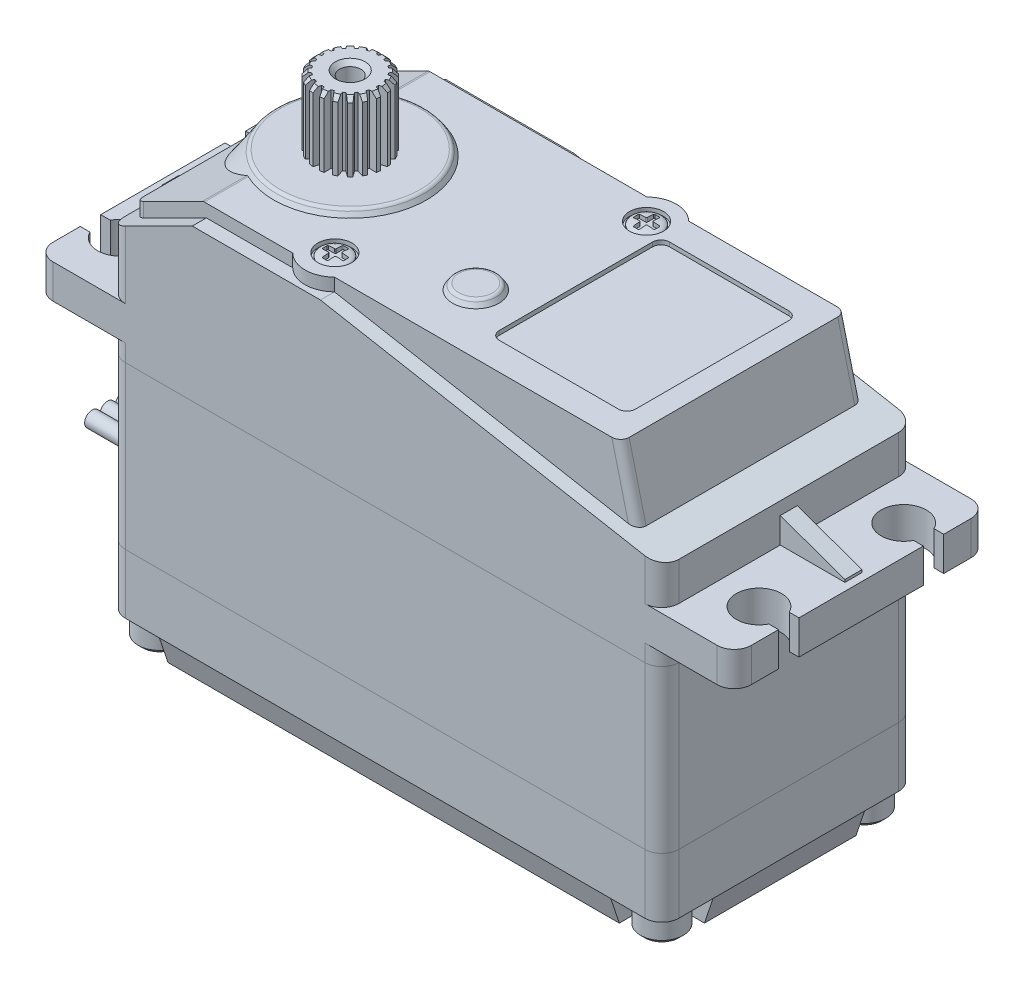
SolidWorks part; units mm, degrees
other "Markup1"
sketch "Sketch20" plane through (60, 8.7, -14.9) normal (0.2547, 0.9537, -0.1598) x (-0.9305, 0.2867, 0.228)
ref_plane "Front Plane" through (0, 0, 0) normal (0, 0, 1) x (1, 0, 0)
ref_plane "Top Plane" through (0, 0, 0) normal (0, 1, 0) x (1, 0, 0)
ref_plane "Right Plane" through (0, 0, 0) normal (1, 0, 0) x (0, 0, -1)
sketch "Sketch1" plane through (0, 0, 0) normal (0, 1, 0) x (1, 0, 0)
  line L0 (11.399, -13.25) -> (47, -13.25)
  line L1 (-12, 13.25) -> (21.601, 13.25)
  line L2 (-12, 13.25) -> (-12, -13.25)
  line L3 (-12, -13.25) -> (6.5, -13.25)
  line L4 (47, 13.25) -> (47, -13.25)
  line L5 (-12, 13.25) -> (47, -13.25) construction
  line L6 (-12, -13.25) -> (47, 13.25) construction
  line L7 (26.5, 13.25) -> (47, 13.25)
  arc A0 (6.5, -13.25) -> (11.399, -13.25) centre (8.9495, -10.75) ccw
  arc A1 (26.5, 13.25) -> (21.601, 13.25) centre (24.0505, 10.75) ccw
  point P0 (17.5, 0)
  dimension "D4" = 7
  dimension "D1" = 59
  dimension "D2" = 26.5
  dimension "D3" = 47
  dimension "D5" = 2.5
  dimension "D6" = 2.5
  dimension "D7" = 18.5
  dimension "D8" = 20.5
extrude "Boss-Extrude1" add sketch "Sketch1" against normal blind 8
chamfer "Chamfer1" distance 4 distance2 8 1 edges at (-12, 0, 0) first distance on face at (-12, -4, 0)
chamfer "Chamfer2" distance 8 distance2 2 1 edges at (47, 0, 0) first distance on face at (47, -4, 0)
fillet "Fillet1" radius 1 4 edges at (46, -4, -13.25) (46, -4, 13.25) (-12, -6, -13.25) (-12, -6, 13.25)
sketch "Sketch2" plane through (0, 0, 0) normal (0, 1, 0) x (1, 0, 0)
  line L0 (21, -8.5) -> (0, -8.5) construction
  circle A0 centre (0, 0) radius 8.5
  circle A1 centre (21, -6.25) radius 2.25
  dimension "D1" = 17
  dimension "D2" = 4.5
  dimension "D3" = 21
extrude "Boss-Extrude2" add sketch "Sketch2" against normal blind 5 draft 34 from offset 0.7 draft outward yes
fillet "Fillet2" radius 0.5 1 edges at (21, 0.7, 8.5)
sketch "Sketch3" plane through (0, 0, 0) normal (0, 0, 1) x (1, 0, 0)
  line L0 (-3.6459, -1.5) -> (-13.5, -6.4271)
  line L1 (-13.5, -6.4271) -> (-13.5, -13.3216)
  line L2 (-13.5, -13.3216) -> (-22, -13.3216)
  line L3 (-22, -13.3216) -> (-22, -17.3216)
  line L4 (-22, -17.3216) -> (-13.5, -17.3216)
  line L5 (-13.5, -17.3216) -> (-13.5, -19.3216)
  line L6 (-13.5, -19.3216) -> (51.5, -19.3216)
  line L7 (51.5, -19.3216) -> (51.5, -17.3216)
  line L8 (51.5, -17.3216) -> (60, -17.3216)
  line L9 (60, -17.3216) -> (60, -13.3216)
  line L10 (60, -13.3216) -> (51.5, -13.3216)
  line L11 (51.5, -13.3216) -> (51.5, -8.8216)
  line L12 (51.5, -8.8216) -> (11.399, -1.5)
  line L13 (11.399, -8) -> (11.399, 0) construction
  line L14 (11.399, -1.5) -> (-3.6459, -1.5)
  line L15 (-4, 0) -> (-11, -3.5) construction
  line L16 (-4, 0) -> (6.5, 0) construction
  line L17 (-12, -8) -> (-12, -4) construction
  dimension "D1" = 2
  dimension "D2" = 4
  dimension "D3" = 4.5
  dimension "D4" = 1.5
  dimension "D5" = 1.5
  dimension "D6" = 1.5
  dimension "D7" = 65
  dimension "D8" = 8.5
extrude "Boss-Extrude3" add sketch "Sketch3" along normal mid plane 29.8
fillet "Fillet3" radius 2 12 edges at (60, -15.3216, -14.9) (60, -15.3216, 14.9) (-22, -15.3216, 14.9) (-22, -15.3216, -14.9) (51.5, -18.3216, 14.9) (51.5, -18.3216, -14.9) (-13.5, -18.3216, 14.9) (-13.5, -18.3216, -14.9) (-13.5, -9.8743, -14.9) (-13.5, -9.8743, 14.9) (51.5, -11.0716, -14.9) (51.5, -11.0716, 14.9)
sketch "Sketch4" plane through (0, 0, 0) normal (0, 1, 0) x (1, 0, 0)
  line L0 (45, -12.25) -> (45, 12.25) construction
  line L1 (27.5, 10) -> (41.5, 10)
  line L2 (26.5, 9) -> (26.5, -9)
  line L3 (27.5, -10) -> (41.5, -10)
  line L4 (42.5, 9) -> (42.5, -9)
  line L5 (26.5, 10) -> (42.5, -10) construction
  line L6 (26.5, -10) -> (42.5, 10) construction
  circle A0 centre (24.0505, 10.75) radius 2
  circle A1 centre (8.9495, -10.75) radius 2
  arc A2 (41.5, 10) -> (42.5, 9) centre (41.5, 9) cw
  arc A3 (27.5, 10) -> (26.5, 9) centre (27.5, 9) ccw
  arc A4 (26.5, -9) -> (27.5, -10) centre (27.5, -9) ccw
  arc A5 (41.5, -10) -> (42.5, -9) centre (41.5, -9) ccw
  point P0 (34.5, 0)
  dimension "D1" = 4
  dimension "D5" = 1
  dimension "D2" = 20
  dimension "D3" = 16
  dimension "D4" = 2.5
extrude "Cut-Extrude1" cut sketch "Sketch4" against normal blind 0.5
sketch "Sketch5" plane through (0, -13.3216, 0) normal (0, 1, 0) x (1, 0, 0)
  line L0 (-22, 0) -> (60, 0) construction
  line L1 (-22, -12.9) -> (-22, 12.9) construction
  line L2 (60, -12.9) -> (60, 12.9) construction
  line L3 (19, 0) -> (19, 21.0756) construction
  line L4 (58.8627, -7.3) -> (60, -7.3)
  line L5 (58.8627, -9.7) -> (60, -9.7)
  line L6 (60, -9.7) -> (60, -7.3)
  line L7 (60, 9.7) -> (60, 7.3)
  line L8 (58.8627, 9.7) -> (60, 9.7)
  line L9 (58.8627, 7.3) -> (60, 7.3)
  line L10 (-20.8627, 7.3) -> (-22, 7.3)
  line L11 (-20.8627, 9.7) -> (-22, 9.7)
  line L12 (-22, 9.7) -> (-22, 7.3)
  line L13 (-22, -9.7) -> (-22, -7.3)
  line L14 (-20.8627, -9.7) -> (-22, -9.7)
  line L15 (-20.8627, -7.3) -> (-22, -7.3)
  arc A0 (58.8627, -7.3) -> (58.8627, -9.7) centre (56.5, -8.5) ccw
  arc A1 (58.8627, 7.3) -> (58.8627, 9.7) centre (56.5, 8.5) cw
  arc A2 (-20.8627, 7.3) -> (-20.8627, 9.7) centre (-18.5, 8.5) ccw
  arc A3 (-20.8627, -7.3) -> (-20.8627, -9.7) centre (-18.5, -8.5) cw
  dimension "D1" = 17
  dimension "D3" = 5.3
  dimension "D2" = 75
  dimension "D4" = 2.4
extrude "Cut-Extrude2" cut sketch "Sketch5" against normal through all
sketch "Sketch6" plane through (0, -19.3216, 0) normal (0, -1, 0) x (1, 0, 0)
  line L4 (51.5, -12.9) -> (51.5, 12.9)
  line L5 (49.5, 14.9) -> (-11.5, 14.9)
  line L6 (-13.5, 12.9) -> (-13.5, -12.9)
  line L7 (-11.5, -14.9) -> (49.5, -14.9)
  line L8 (51.5, -12.9) -> (51.5, 12.9)
  line L9 (49.5, 14.9) -> (-11.5, 14.9)
  line L10 (-13.5, 12.9) -> (-13.5, -12.9)
  line L11 (-11.5, -14.9) -> (49.5, -14.9)
  arc A4 (51.5, 12.9) -> (49.5, 14.9) centre (49.5, 12.9) ccw
  arc A5 (-11.5, 14.9) -> (-13.5, 12.9) centre (-11.5, 12.9) ccw
  arc A6 (-13.5, -12.9) -> (-11.5, -14.9) centre (-11.5, -12.9) ccw
  arc A7 (49.5, -14.9) -> (51.5, -12.9) centre (49.5, -12.9) ccw
  arc A8 (51.5, 12.9) -> (49.5, 14.9) centre (49.5, 12.9) ccw
  arc A9 (-11.5, 14.9) -> (-13.5, 12.9) centre (-11.5, 12.9) ccw
  arc A10 (-13.5, -12.9) -> (-11.5, -14.9) centre (-11.5, -12.9) ccw
  arc A11 (49.5, -14.9) -> (51.5, -12.9) centre (49.5, -12.9) ccw
  dimension "D1" = 0
extrude "Boss-Extrude4" add sketch "Sketch6" along normal blind 19 separate body
sketch "Sketch7" plane through (0, -38.3216, 0) normal (0, -1, 0) x (1, 0, 0)
  line L4 (51.5, -12.9) -> (51.5, 12.9)
  line L5 (49.5, 14.9) -> (-11.5, 14.9)
  line L6 (-13.5, 12.9) -> (-13.5, -12.9)
  line L7 (-11.5, -14.9) -> (49.5, -14.9)
  line L8 (51.5, -12.9) -> (51.5, 12.9)
  line L9 (49.5, 14.9) -> (-11.5, 14.9)
  line L10 (-13.5, 12.9) -> (-13.5, -12.9)
  line L11 (-11.5, -14.9) -> (49.5, -14.9)
  arc A4 (49.5, -14.9) -> (51.5, -12.9) centre (49.5, -12.9) ccw
  arc A5 (51.5, 12.9) -> (49.5, 14.9) centre (49.5, 12.9) ccw
  arc A6 (-11.5, 14.9) -> (-13.5, 12.9) centre (-11.5, 12.9) ccw
  arc A7 (-13.5, -12.9) -> (-11.5, -14.9) centre (-11.5, -12.9) ccw
  arc A8 (49.5, -14.9) -> (51.5, -12.9) centre (49.5, -12.9) ccw
  arc A9 (51.5, 12.9) -> (49.5, 14.9) centre (49.5, 12.9) ccw
  arc A10 (-11.5, 14.9) -> (-13.5, 12.9) centre (-11.5, 12.9) ccw
  arc A11 (-13.5, -12.9) -> (-11.5, -14.9) centre (-11.5, -12.9) ccw
  dimension "D1" = 0
extrude "Boss-Extrude5" add sketch "Sketch7" along normal blind 10 separate body
sketch "Sketch11" plane through (0, 0, 0) normal (0, 0, 1) x (1, 0, 0)
  line L0 (51.5, -10.3216) -> (59.1, -13.0216)
  line L2 (51.5, -13.3216) -> (51.5, -8.8216) construction
  line L3 (58, -13.3216) -> (49.5, -13.3216) construction
  line L5 (19, -19.3216) -> (19, 14.0066) construction
  line L6 (-11.5, -19.3216) -> (49.5, -19.3216) construction
  line L7 (-21.1, -13.0216) -> (-21.1, -13.3216)
  line L8 (59.1, -13.3216) -> (51.5, -13.3216)
  line L9 (51.5, -13.3216) -> (51.5, -10.3216)
  line L10 (51.5, -10.3216) -> (51.5171, -10.3436)
  line L11 (-13.5, -10.3216) -> (-13.5171, -10.3436)
  line L12 (-13.5, -13.3216) -> (-13.5, -10.3216)
  line L13 (-21.1, -13.3216) -> (-13.5, -13.3216)
  line L14 (59.1, -13.0216) -> (59.1, -13.3216)
  line L15 (-13.5, -10.3216) -> (-21.1, -13.0216)
  dimension "D1" = 7.6
  dimension "D2" = 3
  dimension "D3" = 0.3
extrude "Boss-Extrude6" add sketch "Sketch11" along normal mid plane 2 contours L9 L8 L0 | L15 L7 L13 L12 region at (54.2636, -12.3125, 0) region at (-16.2636, -12.3125, 0)
sketch "Sketch12" plane through (0, -48.3216, 0) normal (0, -1, 0) x (1, 0, 0)
  line L0 (65.179, 0) -> (19, 0) construction
  line L1 (49.5, 14.9) -> (-11.5, 14.9) construction
  line L2 (19, 0) -> (19, 14.9) construction
  line L4 (45.5, 14.9) -> (45.5, 8.9)
  line L6 (45.5, 8.9) -> (51.5, 8.9)
  line L9 (45.5, 14.9) -> (49.5, 14.9)
  line L10 (51.5, 12.9) -> (51.5, 8.9)
  line L11 (47.25, -11.1783) -> (48.5, -10.4566)
  line L12 (48.5, 10.4566) -> (49.75, 11.1783)
  line L13 (49.75, 11.1783) -> (49.75, 12.6217)
  line L14 (49.75, 12.6217) -> (48.5, 13.3434)
  line L15 (48.5, 13.3434) -> (47.25, 12.6217)
  line L16 (47.25, 12.6217) -> (47.25, 11.1783)
  line L17 (47.25, 11.1783) -> (48.5, 10.4566)
  line L18 (47.25, -12.6217) -> (47.25, -11.1783)
  line L19 (48.5, -13.3434) -> (47.25, -12.6217)
  line L20 (49.75, -12.6217) -> (48.5, -13.3434)
  line L21 (49.75, -11.1783) -> (49.75, -12.6217)
  line L22 (48.5, -10.4566) -> (49.75, -11.1783)
  line L23 (51.5, -12.9) -> (51.5, -8.9)
  line L24 (45.5, -14.9) -> (49.5, -14.9)
  line L25 (45.5, -8.9) -> (51.5, -8.9)
  line L26 (45.5, -14.9) -> (45.5, -8.9)
  line L27 (-7.5, -14.9) -> (-7.5, -8.9)
  line L28 (-7.5, -8.9) -> (-13.5, -8.9)
  line L29 (-7.5, -14.9) -> (-11.5, -14.9)
  line L30 (-13.5, -12.9) -> (-13.5, -8.9)
  line L31 (-10.5, -10.4566) -> (-11.75, -11.1783)
  line L32 (-11.75, -11.1783) -> (-11.75, -12.6217)
  line L33 (-11.75, -12.6217) -> (-10.5, -13.3434)
  line L34 (-10.5, -13.3434) -> (-9.25, -12.6217)
  line L35 (-9.25, -12.6217) -> (-9.25, -11.1783)
  line L36 (-9.25, 11.1783) -> (-10.5, 10.4566)
  line L37 (-9.25, 12.6217) -> (-9.25, 11.1783)
  line L38 (-10.5, 13.3434) -> (-9.25, 12.6217)
  line L39 (-11.75, 12.6217) -> (-10.5, 13.3434)
  line L40 (-11.75, 11.1783) -> (-11.75, 12.6217)
  line L41 (-10.5, 10.4566) -> (-11.75, 11.1783)
  line L42 (-9.25, -11.1783) -> (-10.5, -10.4566)
  line L43 (-13.5, 12.9) -> (-13.5, 8.9)
  line L44 (-7.5, 14.9) -> (-11.5, 14.9)
  line L45 (-7.5, 8.9) -> (-13.5, 8.9)
  line L46 (-7.5, 14.9) -> (-7.5, 8.9)
  line L47 (49.5, 14.9) -> (-11.5, 14.9) construction
  line L48 (51.5, -12.9) -> (51.5, 12.9) construction
  arc A0 (51.5, 12.9) -> (49.5, 14.9) centre (49.5, 12.9) ccw construction
  arc A1 (51.5, 12.9) -> (49.5, 14.9) centre (49.5, 12.9) ccw
  circle A2 centre (48.5, 11.9) radius 2.5
  circle A3 centre (48.5, 11.9) radius 1.25 construction
  circle A4 centre (48.5, -11.9) radius 1.25 construction
  circle A5 centre (48.5, -11.9) radius 2.5
  arc A6 (51.5, -12.9) -> (49.5, -14.9) centre (49.5, -12.9) cw
  circle A7 centre (-10.5, -11.9) radius 1.25 construction
  circle A8 centre (-10.5, 11.9) radius 1.25 construction
  arc A9 (-13.5, -12.9) -> (-11.5, -14.9) centre (-11.5, -12.9) ccw
  circle A10 centre (-10.5, -11.9) radius 2.5
  circle A11 centre (-10.5, 11.9) radius 2.5
  arc A12 (-13.5, 12.9) -> (-11.5, 14.9) centre (-11.5, 12.9) cw
  point P21 (48.5, 8.9)
  point P23 (45.5, 11.9)
  dimension "D2" = 5
  dimension "D3" = 2.5
  dimension "D1" = 6
extrude "Cut-Extrude3" cut sketch "Sketch12" against normal blind 3 contours A11 L45 L46 | A12 L43 L45 A11 L46 L44 | L41 L36 L37 L38 L39 L40 | A10 L28 L30 A9 L29 L27 | A10 L27 L28 | L35 L42 L31 L32 L33 L34 | A6 L23 L25 A5 L26 L24 | A5 L25 L26 | L22 L11 L18 L19 L20 L21 | L16 L17 L12 L13 L14 L15 | A2 L4 L6 | A2 L6 L10 A1 L9 L4 region at (47.5, -48.3216, 14.8151) region at (48.5, -48.3216, -11.9) region at (48.5, -48.3216, 11.9) region at (50.8542, -48.3216, -14.2542) region at (-9.5, -48.3216, -14.8151) region at (-10.5, -48.3216, -11.9) region at (-10.5, -48.3216, 11.9) region at (-12.8542, -48.3216, 14.2542)
chamfer "Chamfer4" distance 3 distance2 1 4 edges at (51.5, -48.3216, 0) (19, -48.3216, -14.9) (-13.5, -48.3216, 0) (19, -48.3216, 14.9) first distance on face at (51.5, -44.3216, 0) first distance on face at (19, -44.3216, -14.9) first distance on face at (-13.5, -44.3216, 0) first distance on face at (19, -44.3216, 14.9)
chamfer "Chamfer5" distance 0.5 angle 45 4 edges at (-10.5, -48.3216, -14.4) (-10.5, -48.3216, 9.4) (48.5, -48.3216, 9.4) (48.5, -48.3216, -14.4)
sketch "Sketch13" plane through (0, 0.7, 0) normal (0, 1, 0) x (1, 0, 0)
  circle A0 centre (0, 0) radius 4
  circle A1 centre (0, 0) radius 1.25
  dimension "D1" = 8
  dimension "D2" = 2.5
extrude "Boss-Extrude7" add sketch "Sketch13" along normal blind 8 separate body
chamfer "Chamfer6" distance 0.5 angle 45 2 edges at (0, 8.7, 4) (0, 8.7, 1.25)
sketch "Sketch14" plane through (0, 8.7, 0) normal (0, 1, 0) x (1, 0, 0)
  line L0 (3.9799, 0.4) -> (3.2, 0.15)
  line L1 (3.2, 0.15) -> (3.2, -0.15)
  line L2 (3.2, -0.15) -> (3.9799, -0.4)
  line L3 (3.2, 0) -> (0, 0) construction
  line L4 (3.9088, -0.8494) -> (3.0897, -0.8462)
  line L5 (3.0897, -0.8462) -> (2.997, -1.1315)
  line L6 (2.997, -1.1315) -> (3.6616, -1.6103)
  line L7 (3.455, -2.0157) -> (2.677, -1.7596)
  line L8 (2.677, -1.7596) -> (2.5007, -2.0023)
  line L9 (2.5007, -2.0023) -> (2.9847, -2.663)
  line L10 (2.663, -2.9847) -> (2.0023, -2.5007)
  line L11 (2.0023, -2.5007) -> (1.7596, -2.677)
  line L12 (1.7596, -2.677) -> (2.0157, -3.455)
  line L13 (1.6103, -3.6616) -> (1.1315, -2.997)
  line L14 (1.1315, -2.997) -> (0.8462, -3.0897)
  line L15 (0.8462, -3.0897) -> (0.8494, -3.9088)
  line L16 (0.4, -3.9799) -> (0.15, -3.2)
  line L17 (0.15, -3.2) -> (-0.15, -3.2)
  line L18 (-0.15, -3.2) -> (-0.4, -3.9799)
  line L19 (-0.8494, -3.9088) -> (-0.8462, -3.0897)
  line L20 (-0.8462, -3.0897) -> (-1.1315, -2.997)
  line L21 (-1.1315, -2.997) -> (-1.6103, -3.6616)
  line L22 (-2.0157, -3.455) -> (-1.7596, -2.677)
  line L23 (-1.7596, -2.677) -> (-2.0023, -2.5007)
  line L24 (-2.0023, -2.5007) -> (-2.663, -2.9847)
  line L25 (-2.9847, -2.663) -> (-2.5007, -2.0023)
  line L26 (-2.5007, -2.0023) -> (-2.677, -1.7596)
  line L27 (-2.677, -1.7596) -> (-3.455, -2.0157)
  line L28 (-3.6616, -1.6103) -> (-2.997, -1.1315)
  line L29 (-2.997, -1.1315) -> (-3.0897, -0.8462)
  line L30 (-3.0897, -0.8462) -> (-3.9088, -0.8494)
  line L31 (-3.9799, -0.4) -> (-3.2, -0.15)
  line L32 (-3.2, -0.15) -> (-3.2, 0.15)
  line L33 (-3.2, 0.15) -> (-3.9799, 0.4)
  line L34 (-3.9088, 0.8494) -> (-3.0897, 0.8462)
  line L35 (-3.0897, 0.8462) -> (-2.997, 1.1315)
  line L36 (-2.997, 1.1315) -> (-3.6616, 1.6103)
  line L37 (-3.455, 2.0157) -> (-2.677, 1.7596)
  line L38 (-2.677, 1.7596) -> (-2.5007, 2.0023)
  line L39 (-2.5007, 2.0023) -> (-2.9847, 2.663)
  line L40 (-2.663, 2.9847) -> (-2.0023, 2.5007)
  line L41 (-2.0023, 2.5007) -> (-1.7596, 2.677)
  line L42 (-1.7596, 2.677) -> (-2.0157, 3.455)
  line L43 (-1.6103, 3.6616) -> (-1.1315, 2.997)
  line L44 (-1.1315, 2.997) -> (-0.8462, 3.0897)
  line L45 (-0.8462, 3.0897) -> (-0.8494, 3.9088)
  line L46 (-0.4, 3.9799) -> (-0.15, 3.2)
  line L47 (-0.15, 3.2) -> (0.15, 3.2)
  line L48 (0.15, 3.2) -> (0.4, 3.9799)
  line L49 (0.8494, 3.9088) -> (0.8462, 3.0897)
  line L50 (0.8462, 3.0897) -> (1.1315, 2.997)
  line L51 (1.1315, 2.997) -> (1.6103, 3.6616)
  line L52 (2.0157, 3.455) -> (1.7596, 2.677)
  line L53 (1.7596, 2.677) -> (2.0023, 2.5007)
  line L54 (2.0023, 2.5007) -> (2.663, 2.9847)
  line L55 (2.9847, 2.663) -> (2.5007, 2.0023)
  line L56 (2.5007, 2.0023) -> (2.677, 1.7596)
  line L57 (2.677, 1.7596) -> (3.455, 2.0157)
  line L58 (3.6616, 1.6103) -> (2.997, 1.1315)
  line L59 (2.997, 1.1315) -> (3.0897, 0.8462)
  line L60 (3.0897, 0.8462) -> (3.9088, 0.8494)
  circle A0 centre (0, 0) radius 4 construction
  arc A1 (3.9799, -0.4) -> (3.9799, 0.4) centre (0, 0) ccw
  arc A2 (3.6616, -1.6103) -> (3.9088, -0.8494) centre (0, 0) ccw
  arc A3 (2.9847, -2.663) -> (3.455, -2.0157) centre (0, 0) ccw
  arc A4 (2.0157, -3.455) -> (2.663, -2.9847) centre (0, 0) ccw
  arc A5 (0.8494, -3.9088) -> (1.6103, -3.6616) centre (0, 0) ccw
  arc A6 (-0.4, -3.9799) -> (0.4, -3.9799) centre (0, 0) ccw
  arc A7 (-1.6103, -3.6616) -> (-0.8494, -3.9088) centre (0, 0) ccw
  arc A8 (-2.663, -2.9847) -> (-2.0157, -3.455) centre (0, 0) ccw
  arc A9 (-3.455, -2.0157) -> (-2.9847, -2.663) centre (0, 0) ccw
  arc A10 (-3.9088, -0.8494) -> (-3.6616, -1.6103) centre (0, 0) ccw
  arc A11 (-3.9799, 0.4) -> (-3.9799, -0.4) centre (0, 0) ccw
  arc A12 (-3.6616, 1.6103) -> (-3.9088, 0.8494) centre (0, 0) ccw
  arc A13 (-2.9847, 2.663) -> (-3.455, 2.0157) centre (0, 0) ccw
  arc A14 (-2.0157, 3.455) -> (-2.663, 2.9847) centre (0, 0) ccw
  arc A15 (-0.8494, 3.9088) -> (-1.6103, 3.6616) centre (0, 0) ccw
  arc A16 (0.4, 3.9799) -> (-0.4, 3.9799) centre (0, 0) ccw
  arc A17 (1.6103, 3.6616) -> (0.8494, 3.9088) centre (0, 0) ccw
  arc A18 (2.663, 2.9847) -> (2.0157, 3.455) centre (0, 0) ccw
  arc A19 (3.455, 2.0157) -> (2.9847, 2.663) centre (0, 0) ccw
  arc A20 (3.9088, 0.8494) -> (3.6616, 1.6103) centre (0, 0) ccw
  point P85 (0, 0)
  dimension "D1" = 0.3
  dimension "D2" = 0.8
  dimension "D3" = 3.2
  dimension "D4" = 20
extrude "Cut-Extrude4" cut sketch "Sketch14" against normal through all
sketch "Sketch15" plane through (0, -0.5, 0) normal (0, 1, 0) x (1, 0, 0)
  circle A0 centre (8.9495, -10.75) radius 1.75
  circle A1 centre (8.9495, -10.75) radius 2 construction
  circle A2 centre (24.0505, 10.75) radius 2 construction
  circle A5 centre (24.0505, 10.75) radius 1.75
  dimension "D1" = 3.5
extrude "Boss-Extrude8" add sketch "Sketch15" along normal blind 0.5 separate body
fillet "Fillet4" radius 0.32 1 edges at (8.9495, 0, 12.5) second distance 1.2 first distance on face at (8.9495, 0, 12.5)
fillet "Fillet5" radius 0.32 1 edges at (24.0505, 0, -9) second distance 1.2 first distance on face at (24.0505, 0, -9)
sketch "Sketch16" plane through (0, 0, 0) normal (0, 1, 0) x (1, 0, 0)
  line L0 (8.607, -9.4483) -> (9.307, -9.4483)
  line L1 (23.7005, 12) -> (24.4005, 12)
  line L2 (23.7005, 12) -> (23.7005, 9.5)
  line L3 (23.7005, 9.5) -> (24.4005, 9.5)
  line L4 (24.4005, 12) -> (24.4005, 9.5)
  line L5 (23.7005, 12) -> (24.4005, 9.5) construction
  line L6 (23.7005, 9.5) -> (24.4005, 12) construction
  line L7 (22.8005, 11.1) -> (25.3005, 11.1)
  line L8 (22.8005, 11.1) -> (22.8005, 10.4)
  line L9 (22.8005, 10.4) -> (25.3005, 10.4)
  line L10 (25.3005, 11.1) -> (25.3005, 10.4)
  line L11 (22.8005, 11.1) -> (25.3005, 10.4) construction
  line L12 (22.8005, 10.4) -> (25.3005, 11.1) construction
  line L13 (8.607, -9.4483) -> (8.607, -11.9483)
  line L14 (8.607, -11.9483) -> (9.307, -11.9483)
  line L15 (9.307, -9.4483) -> (9.307, -11.9483)
  line L16 (8.607, -9.4483) -> (9.307, -11.9483) construction
  line L17 (8.607, -11.9483) -> (9.307, -9.4483) construction
  line L18 (7.707, -10.3483) -> (10.207, -10.3483)
  line L19 (7.707, -10.3483) -> (7.707, -11.0483)
  line L20 (7.707, -11.0483) -> (10.207, -11.0483)
  line L21 (10.207, -10.3483) -> (10.207, -11.0483)
  line L22 (7.707, -10.3483) -> (10.207, -11.0483) construction
  line L23 (7.707, -11.0483) -> (10.207, -10.3483) construction
  point P0 (24.0505, 10.75)
  point P5 (24.0505, 10.75)
  point P11 (8.957, -10.6983)
  point P16 (8.957, -10.6983)
  dimension "D1" = 2.5
  dimension "D2" = 0.7
  dimension "D3" = 2.5
  dimension "D4" = 0.7
extrude "Cut-Extrude5" cut sketch "Sketch16" against normal blind 0.48 contours L15 L14 L13 L0 | L20 L21 L18 L19 | L9 L10 L7 L8 | L4 L3 L2 L1
fillet "Fillet6" radius 0.1 12 edges at (24.4005, -0.24, -10.4) (24.4005, -0.24, -11.1) (23.7005, -0.24, -10.4) (23.7005, -0.24, -11.1) (23.7005, -0.2749, -12) (24.4005, -0.2749, -12) (25.3005, -0.2749, -11.1) (25.3005, -0.2749, -10.4) (24.4005, -0.2749, -9.5) (23.7005, -0.2749, -9.5) (22.8005, -0.2749, -10.4) (22.8005, -0.2749, -11.1)
fillet "Fillet7" radius 0.1 12 edges at (10.207, -0.2773, 10.3483) (9.307, -0.2701, 11.9483) (10.207, -0.2743, 11.0483) (7.707, -0.2728, 11.0483) (8.607, -0.2697, 11.9483) (9.307, -0.24, 11.0483) (8.607, -0.24, 11.0483) (7.707, -0.2757, 10.3483) (8.607, -0.2803, 9.4483) (8.607, -0.24, 10.3483) (9.307, -0.24, 10.3483) (9.307, -0.2807, 9.4483)
fillet "Fillet8" radius 0.5 3 edges at (0, 0.7, 8.5) (-4, 0, -10.6406) (-4, 0, 10.6406)
sketch "Sketch17" plane through (-13.5, 0, 0) normal (-1, 0, 0) x (0, 0, 1)
  line L0 (12.9, -38.3216) -> (-12.9, -38.3216) construction
  line L1 (3.4, -38.3216) -> (-3.4, -38.3216)
  line L2 (3.4, -38.3216) -> (3.4, -41.8216)
  line L3 (3.4, -41.8216) -> (-3.4, -41.8216)
  line L4 (-3.4, -38.3216) -> (-3.4, -41.8216)
  line L5 (0, -38.3216) -> (0, 0) construction
  dimension "D1" = 6.8
  dimension "D2" = 3.5
extrude "Boss-Extrude9" add sketch "Sketch17" along normal blind 1 separate body
sketch "Sketch18" plane through (-14.5, 0, 0) normal (-1, 0, 0) x (0, 0, 1)
  line L4 (3.4, -41.8216) -> (3.4, -38.3216)
  line L5 (3.4, -38.3216) -> (-3.4, -38.3216)
  line L6 (-3.4, -38.3216) -> (-3.4, -41.8216)
  line L7 (-3.4, -41.8216) -> (3.4, -41.8216)
  line L8 (3.4, -41.8216) -> (3.4, -38.3216)
  line L9 (3.4, -38.3216) -> (-3.4, -38.3216)
  line L10 (-3.4, -38.3216) -> (-3.4, -41.8216)
  line L11 (-3.4, -41.8216) -> (3.4, -41.8216)
  dimension "D1" = 0
extrude "Boss-Extrude10" add sketch "Sketch18" along normal blind 4 draft 10
sketch "Sketch19" plane through (-18.5, 0, 0) normal (-1, 0, 0) x (0, 0, 1)
  line L0 (0, -40.0716) -> (0, -39.0269) construction
  line L1 (2.6947, -39.0269) -> (-2.6947, -39.0269) construction
  line L2 (0, -40.0716) -> (0, -41.1163) construction
  line L3 (-2.6947, -41.1163) -> (2.6947, -41.1163) construction
  circle A0 centre (0, -40.0716) radius 0.89
  circle A1 centre (1.8, -40.0716) radius 0.89
  circle A2 centre (-1.8, -40.0716) radius 0.89
  dimension "D1" = 1.78
  dimension "D2" = 1.8
extrude "Boss-Extrude12" add sketch "Sketch19" along normal blind 10
